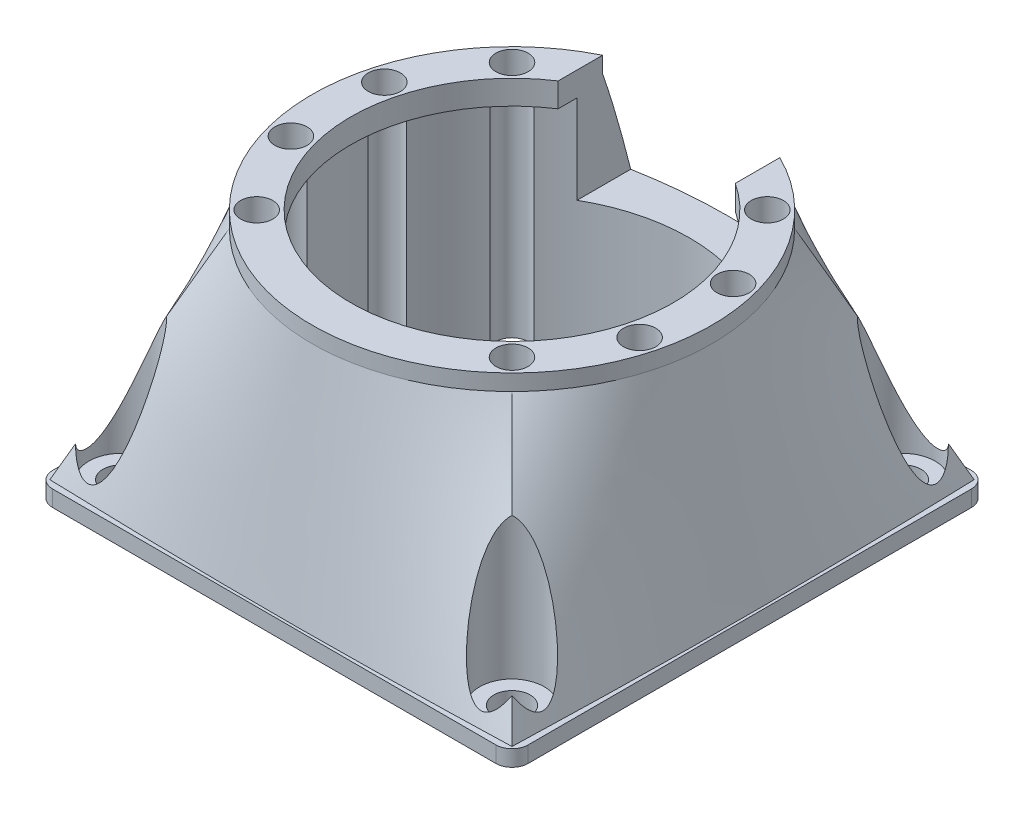
SolidWorks part; units mm, degrees
material "Esun Hard Tough Resin"
ref_plane "Front Plane" through (0, 0, 0) normal (0, 0, 1) x (1, 0, 0)
ref_plane "Top Plane" through (0, 0, 0) normal (0, 1, 0) x (1, 0, 0)
ref_plane "Right Plane" through (0, 0, 0) normal (1, 0, 0) x (0, 0, -1)
sketch "Sketch1" plane through (0, 0, 0) normal (0, 1, 0) x (1, 0, 0)
  line L5 (-14.75, -14.75) -> (14.75, -14.75)
  line L6 (-14.75, -14.75) -> (-14.75, 14.75)
  line L7 (-14.75, 14.75) -> (14.75, 14.75)
  line L8 (14.75, -14.75) -> (14.75, 14.75)
  line L9 (-14.75, -14.75) -> (14.75, 14.75) construction
  line L10 (-14.75, 14.75) -> (14.75, -14.75) construction
  point P0 (0, 0)
  dimension "D1" = 29.5
ref_plane "Plane1" through (0, 14.5, 0) normal (0, 1, 0) x (1, 0, 0)
sketch "Sketch2" plane through (0, 14.5, 0) normal (0, 1, 0) x (1, 0, 0)
  line L0 (-14.75, -14.75) -> (14.75, 14.75) construction
  circle A0 centre (0, 0) radius 12.4
  dimension "D1" = 24.8
sketch "Sketch3" plane through (0, 0, 0) normal (0, 1, 0) x (1, 0, 0)
  line L0 (-14.75, -14.75) -> (14.75, 14.75) construction
  line L1 (14.75, -14.75) -> (-14.75, -14.75)
  line L2 (14.75, -14.75) -> (14.75, 14.75)
  line L3 (14.75, 14.75) -> (-14.75, 14.75)
  line L4 (-14.75, -14.75) -> (-14.75, 14.75)
  line L5 (14.75, -14.75) -> (-14.75, 14.75) construction
  line L6 (14.75, 14.75) -> (-14.75, -14.75) construction
  line L7 (-14.75, 14.75) -> (14.75, -14.75) construction
  dimension "D1" = 29.5
loft "Loft3" add profiles "Sketch2", "Sketch3" connector at (-9.3527, 14.5, 8.1417) connector at (-14.75, 0, -14.75)
sketch "Sketch5" plane through (0, 14.5, 0) normal (0, 1, 0) x (1, 0, 0)
  circle A0 centre (0, 0) radius 12.4
  dimension "D1" = 24.8
extrude "Boss-Extrude1" add sketch "Sketch5" along normal blind 1
sketch "Sketch6" plane through (0, 15.5, 0) normal (0, 1, 0) x (1, 0, 0)
  circle A0 centre (0, 0) radius 10
  dimension "D1" = 20
sketch "Sketch8" plane through (0, 15.5, 0) normal (0, 1, 0) x (1, 0, 0)
  line L0 (-14.75, 14.75) -> (14.75, -14.75) construction
  line L1 (0, -7.9774) -> (0, 7.9774) construction
  circle A0 centre (0, 0) radius 11.2 construction
  circle A1 centre (-7.9196, 7.9196) radius 1
  circle A2 centre (-10.8184, 2.8988) radius 1
  circle A5 centre (-10.8184, -2.8988) radius 1
  circle A6 centre (-7.9196, -7.9196) radius 1
  circle A7 centre (7.9196, -7.9196) radius 1
  circle A8 centre (10.8184, -2.8988) radius 1
  circle A9 centre (10.8184, 2.8988) radius 1
  circle A10 centre (7.9196, 7.9196) radius 1
  point P15 (0, 0)
  dimension "D1" = 2
  dimension "D2" = 22.4
  dimension "D3" = 4
extrude "Cut-Extrude1" cut sketch "Sketch6" against normal through all both and the other way through all
extrude "Cut-Extrude2" cut sketch "Sketch8" against normal blind 23.5 and the other way through all
sketch "Sketch11" plane through (0, 0, 0) normal (0, 1, 0) x (1, 0, 0)
  line L0 (-12.125, 12.125) -> (-12.125, -12.125) construction
  line L1 (-12.125, -12.125) -> (12.125, -12.125) construction
  line L2 (12.125, -12.125) -> (12.125, 12.125) construction
  line L3 (12.125, 12.125) -> (-12.125, 12.125) construction
  line L4 (-12.125, 12.125) -> (12.125, -12.125) construction
  line L5 (-12.125, -12.125) -> (12.125, 12.125) construction
  line L6 (-14.75, 14.75) -> (14.75, -14.75) construction
  line L7 (-14.75, -14.75) -> (14.75, 14.75) construction
  line L13 (14.75, -14.75) -> (-14.75, 14.75) construction
  line L14 (14.75, 14.75) -> (-14.75, -14.75) construction
  circle A0 centre (-12.125, 12.125) radius 1.125
  circle A1 centre (-12.125, -12.125) radius 1.125
  circle A2 centre (12.125, -12.125) radius 1.125
  circle A3 centre (12.125, 12.125) radius 1.125
  circle A4 centre (0, 0) radius 11
  dimension "D2" = 2.25
  dimension "D3" = 22
  dimension "D1" = 24.25
extrude "Boss-Extrude3" add sketch "Sketch1" along normal blind 1
extrude "Cut-Extrude4" cut sketch "Sketch11" against normal blind 8 and the other way blind 14
sketch "Sketch12" plane through (0, 1, 0) normal (0, 1, 0) x (1, 0, 0)
  circle A0 centre (-7.9196, 7.9196) radius 1
  circle A1 centre (-10.8184, 2.8988) radius 1
  circle A2 centre (-10.8184, -2.8988) radius 1
  circle A3 centre (-7.9196, -7.9196) radius 1
  circle A4 centre (7.9196, -7.9196) radius 1
  circle A5 centre (10.8184, -2.8988) radius 1
  circle A6 centre (10.8184, 2.8988) radius 1
  circle A7 centre (7.9196, 7.9196) radius 1
extrude "Cut-Extrude5" cut sketch "Sketch12" against normal through all both and the other way through all
sketch "Sketch13" plane through (0, 1, 0) normal (0, 1, 0) x (1, 0, 0)
  circle A0 centre (-12.125, 12.125) radius 2
  circle A1 centre (12.125, 12.125) radius 2
  circle A2 centre (12.125, -12.125) radius 2
  circle A3 centre (-12.125, -12.125) radius 2
  dimension "D1" = 4
extrude "Cut-Extrude6" cut sketch "Sketch13" along normal through all
sketch "Sketch15" plane through (0, 0, 0) normal (0, 0, 1) x (1, 0, 0)
  line L0 (10, 15.5) -> (-10, 15.5) construction
  line L1 (-5.4952, 8.5) -> (5.5048, 8.5)
  line L2 (-5.4952, 8.5) -> (-5.4952, 15.5)
  line L3 (-5.4952, 15.5) -> (5.5048, 15.5)
  line L4 (5.5048, 8.5) -> (5.5048, 15.5)
  line L5 (-5.4952, 8.5) -> (5.5048, 15.5) construction
  line L6 (-5.4952, 15.5) -> (5.5048, 8.5) construction
  point P0 (0.0048, 12)
  dimension "D1" = 11
  dimension "D2" = 7
extrude "Cut-Extrude7" cut sketch "Sketch15" against normal through all
fillet "Fillet1" radius 1 4 edges
